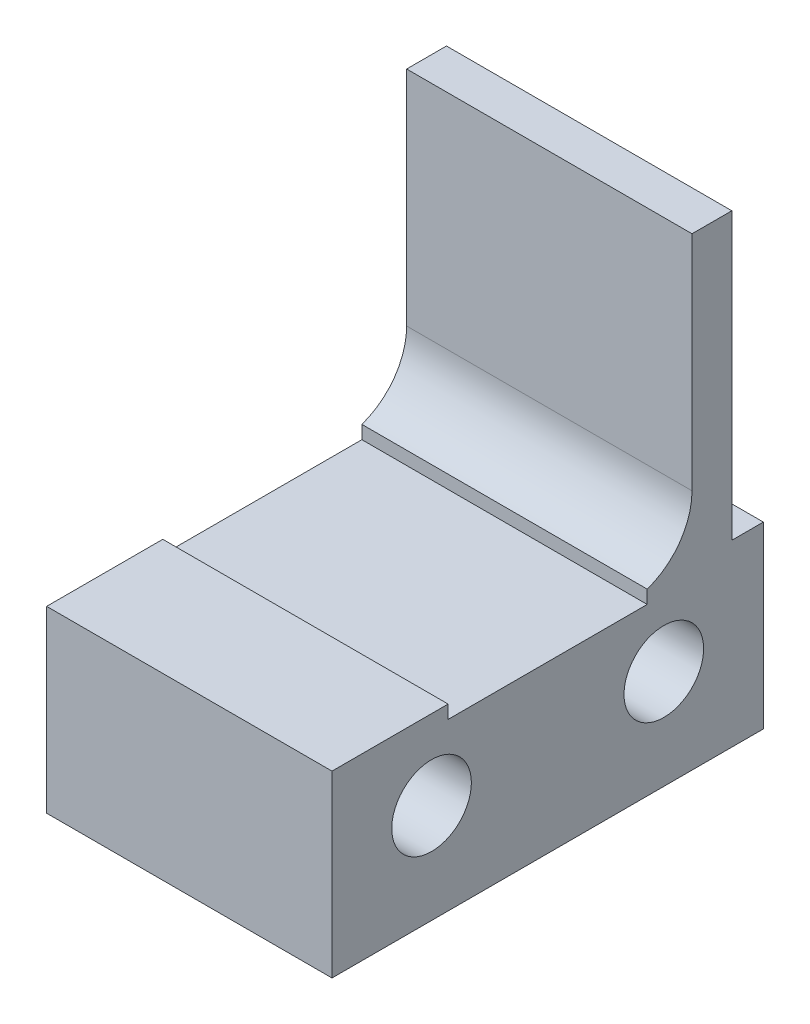
SolidWorks part; units mm, degrees
ref_plane "Front Plane" through (0, 0, 0) normal (0, 0, 1) x (1, 0, 0)
ref_plane "Top Plane" through (0, 0, 0) normal (0, 1, 0) x (1, 0, 0)
ref_plane "Right Plane" through (0, 0, 0) normal (1, 0, 0) x (0, 0, -1)
sketch "Sketch9" plane through (0, 0, 0) normal (0, 0, 1) x (1, 0, 0)
  line L0 (0, 0) -> (0, 27) construction
  line L1 (21.5, 27) -> (-21.5, 27)
  line L2 (-21.5, 27) -> (-21.5, 0)
  line L3 (-21.5, 0) -> (21.5, 0)
  line L4 (21.5, 27) -> (21.5, 0)
  dimension "D1" = 43
  dimension "D2" = 27
extrude "Boss-Extrude1" add sketch "Sketch9" along normal mid plane 65
sketch "Sketch10" plane through (21.5, 0, 0) normal (1, 0, 0) x (0, 0, -1)
  line L0 (0, 27) -> (0, 0) construction
  line L1 (-32.5, 27) -> (32.5, 27) construction
  line L2 (-32.5, 0) -> (32.5, 0) construction
  circle A0 centre (-17.5, 15) radius 6
  circle A1 centre (17.5, 15) radius 6
  dimension "D1" = 12
  dimension "D2" = 35
  dimension "D3" = 15
extrude "Cut-Extrude1" cut sketch "Sketch10" against normal through all both and the other way through all
sketch "Sketch11" plane through (0, 0, 0) normal (0, -1, 0) x (1, 0, 0)
  line L0 (0, 32.5) -> (0, -32.5) construction
  line L1 (-21.5, 32.5) -> (21.5, 32.5) construction
  line L2 (-21.5, -32.5) -> (21.5, -32.5) construction
  line L3 (21.5, 0) -> (-21.5, 0) construction
  line L4 (21.5, 32.5) -> (21.5, -32.5) construction
  line L5 (-21.5, 32.5) -> (-21.5, -32.5) construction
  line L6 (12, -12) -> (13.5, -9.4019)
  line L7 (13.5, 9.4019) -> (16.5, 9.4019)
  line L8 (16.5, 9.4019) -> (18, 12)
  line L9 (18, 12) -> (16.5, 14.5981)
  line L10 (16.5, 14.5981) -> (13.5, 14.5981)
  line L11 (13.5, 14.5981) -> (12, 12)
  line L12 (12, 12) -> (13.5, 9.4019)
  line L13 (13.5, -14.5981) -> (12, -12)
  line L14 (16.5, -14.5981) -> (13.5, -14.5981)
  line L15 (18, -12) -> (16.5, -14.5981)
  line L16 (16.5, -9.4019) -> (18, -12)
  line L17 (13.5, -9.4019) -> (16.5, -9.4019)
  line L18 (-13.5, -9.4019) -> (-16.5, -9.4019)
  line L19 (-16.5, -9.4019) -> (-18, -12)
  line L20 (-18, -12) -> (-16.5, -14.5981)
  line L21 (-16.5, -14.5981) -> (-13.5, -14.5981)
  line L22 (-13.5, -14.5981) -> (-12, -12)
  line L23 (-12, -12) -> (-13.5, -9.4019)
  line L24 (-12, 12) -> (-13.5, 9.4019)
  line L25 (-13.5, 14.5981) -> (-12, 12)
  line L26 (-16.5, 14.5981) -> (-13.5, 14.5981)
  line L27 (-18, 12) -> (-16.5, 14.5981)
  line L28 (-16.5, 9.4019) -> (-18, 12)
  line L29 (-13.5, 9.4019) -> (-16.5, 9.4019)
  circle A0 centre (15, 12) radius 2.5981 construction
  circle A1 centre (15, -12) radius 2.5981 construction
  circle A2 centre (-15, -12) radius 2.5981 construction
  circle A3 centre (-15, 12) radius 2.5981 construction
  dimension "D1" = 3
  dimension "D2" = 24
  dimension "D3" = 30
extrude "Cut-Extrude2" cut sketch "Sketch11" against normal blind 3
sketch "Sketch14" plane through (21.5, 0, 0) normal (1, 0, 0) x (0, 0, -1)
  line L0 (0, 27) -> (0, 0) construction
  line L1 (-32.5, 27) -> (32.5, 27) construction
  line L2 (-32.5, 0) -> (32.5, 0) construction
  line L3 (-15, 27) -> (-15, 25)
  line L4 (-15, 25) -> (15, 25)
  line L5 (15, 27) -> (15, 25)
  line L6 (-15, 27) -> (15, 27)
  point P10 (0, 25)
  dimension "D1" = 30
  dimension "D2" = 2
extrude "Cut-Extrude4" cut sketch "Sketch14" against normal through all both and the other way through all
sketch "Sketch15" plane through (0, 27, 0) normal (0, 1, 0) x (1, 0, 0)
  line L7 (-21.5, 27.75) -> (21.5, 27.75)
  line L8 (-21.5, 15) -> (-21.5, 32.5) construction
  line L9 (21.5, 15) -> (21.5, 32.5) construction
  line L10 (21.5, 21.75) -> (-21.5, 21.75)
  line L11 (-21.5, 21.75) -> (-21.5, 27.75)
  line L12 (21.5, 32.5) -> (-21.5, 32.5) construction
  line L13 (21.5, 21.75) -> (21.5, 27.75)
  dimension "D3" = 4.75
  dimension "D4" = 6
extrude "Boss-Extrude2" add sketch "Sketch15" along normal blind 43
hole_wizard "Ø3.0mm Dowel Hole1" positions "3DSketch3" profile "Sketch19" hole size "Ø3.0" standard "ISO"
sketch3d "3DSketch3"
  line L3 (-13.5, 0, -14.5981) -> (-16.5, 0, -9.4019) construction
  line L5 (16.5, 0, -14.5981) -> (13.5, 0, -9.4019) construction
  line L7 (16.5, 0, 9.4019) -> (13.5, 0, 14.5981) construction
  line L9 (-16.5, 0, 14.5981) -> (-13.5, 0, 9.4019) construction
  point P27 (-15, 0, 12)
  point P29 (-15, 0, -12)
  point P31 (15, 0, -12)
  point P33 (15, 0, 12)
  point P36 (0, 0, 0)
  point P37 (0, 0, 0)
  point P38 (0, 0, 0)
  point P39 (0, 0, 0)
sketch "Sketch19" plane through (15, 0, 12) normal (1, 0, 0) x (0, 0, -1)
  line L0 (0, 0) -> (0, 6.9013)
  line L1 (0, 6.9013) -> (1.5, 6)
  line L2 (1.5, 6) -> (1.5, 0)
  line L5 (1.5, 0) -> (0, 0)
  line L10 (0, 6.9013) -> (-1.5, 6) construction
  line L11 (0, -6.35) -> (0, 107.95) construction
  dimension "Hole Dia." = 3
  dimension "Hole Depth" = 6
  dimension "Drill Angle" = 118
fillet "Fillet2" radius 10 1 edges at (0, 27, -21.75)
